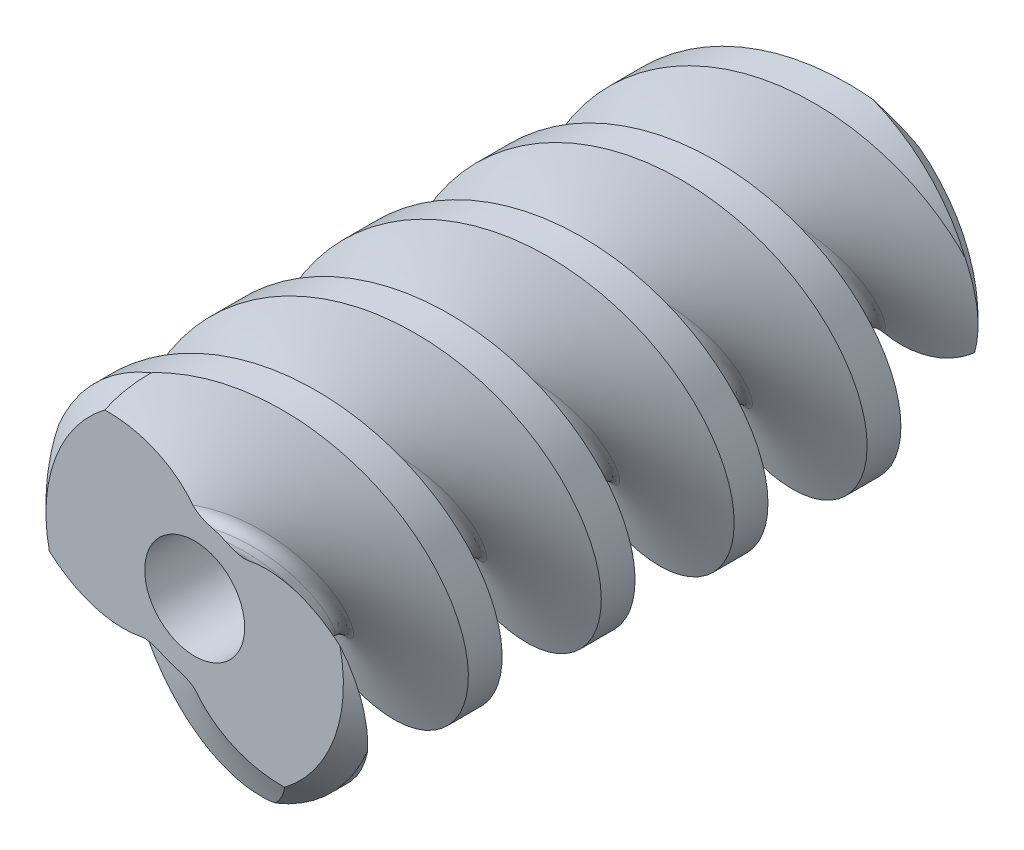
SolidWorks part; units mm, degrees
ref_plane "Front" through (0, 0, 0) normal (0, 0, 1) x (1, 0, 0)
ref_plane "Top" through (0, 0, 0) normal (0, 1, 0) x (1, 0, 0)
ref_plane "Right" through (0, 0, 0) normal (1, 0, 0) x (0, 0, -1)
ref_axis "Axis1" through (0, 0, 50) along (0, 0, -1)
sketch "SketchRevolveWorm01" plane through (0, 0, 0) normal (1, 0, 0) x (0, 0, -1)
  line L0 (0, 0) -> (1, 0) construction
  line L1 (19.05, 0) -> (19.05, 8.928)
  line L2 (19.05, 8.928) -> (17.938, 10.04)
  line L3 (17.938, 10.04) -> (-17.938, 10.04)
  line L4 (-17.938, 10.04) -> (-19.05, 8.928)
  line L5 (-19.05, 8.928) -> (-19.05, 0)
  line L6 (-19.05, 0) -> (19.05, 0)
  dimension "Side1" = 19.05
  dimension "ChamferX" = 1.112
  dimension "ChamferY" = 1.112
  dimension "OutsideDiameter" = 10.04
  dimension "WormLength" = 38.1
revolve "Worm01" add sketch "SketchRevolveWorm01" angle 360 about L0
ref_plane "HelixPlaneWorm01" through (0, 0, 31.9186) normal (0, 0, 1) x (1, 0, 0)
sketch "SketchHelixWorm01" plane through (0, 0, 31.9186) normal (0, 0, 1) x (1, 0, 0)
  circle A0 centre (0, 0) radius 7.5
  dimension "PitchDiameter" = 15
curve "GearHelixWorm01" pitch 15.9593 height 63.8372 radius 7.5 centre (0, 0, 31.9186) axis (0, 0, -1) start towards (1, 0, 0)
sketch "SketchToothWorm01" plane through (0, 0, 0) normal (0, 1, 0) x (1, 0, 0)
  line L0 (10.675, -28.6975) -> (4.8125, -30.9615)
  line L1 (4.325, -31.6724) -> (4.325, -32.1648)
  line L2 (4.8125, -32.8756) -> (10.675, -35.1396)
  line L3 (10.675, -35.1396) -> (10.675, -28.6975)
  arc A0 (4.8125, -30.9615) -> (4.325, -31.6724) centre (5.087, -31.6724) ccw
  arc A1 (4.325, -32.1648) -> (4.8125, -32.8756) centre (5.087, -32.1648) ccw
sweep "ToothCutWorm01" cut profiles "SketchToothWorm01" path "GearHelixWorm01" align with end faces yes
pattern_circular "PatternThreadWorm01" count 2 every 180 about axis through (0, 0, 50) along (0, 0, -1) of "ToothCutWorm01"
sketch "BoreRevolveSketch" plane through (0, 0, 0) normal (1, 0, 0) x (0, 0, -1)
  line L0 (-19.05, 0) -> (19.05, 0)
  line L1 (19.05, 0) -> (19.05, 4.7625)
  line L2 (19.05, 4.7625) -> (-19.05, 4.7625)
  line L3 (-19.05, 4.7625) -> (-19.05, 0)
  dimension "BoreSide1" = 19.05
  dimension "TaperSide1" = 4.7625
  dimension "BoreSide2" = 19.05
  dimension "TaperSide2" = 4.7625
sketch "AuxiliarySketchWorm01" plane through (0, 0, 0) normal (0, 0, 1) x (1, 0, 0)
  circle A0 centre (0, 0) radius 7.5 construction
  dimension "PitchDiameter" = 15
sketch "Sketch7" plane through (0, 0, 19.05) normal (0, 0, 1) x (1, 0, 0)
  circle A0 centre (0, 0) radius 3
  dimension "D1" = 6
extrude "Cut-Extrude2" cut sketch "Sketch7" against normal through all
